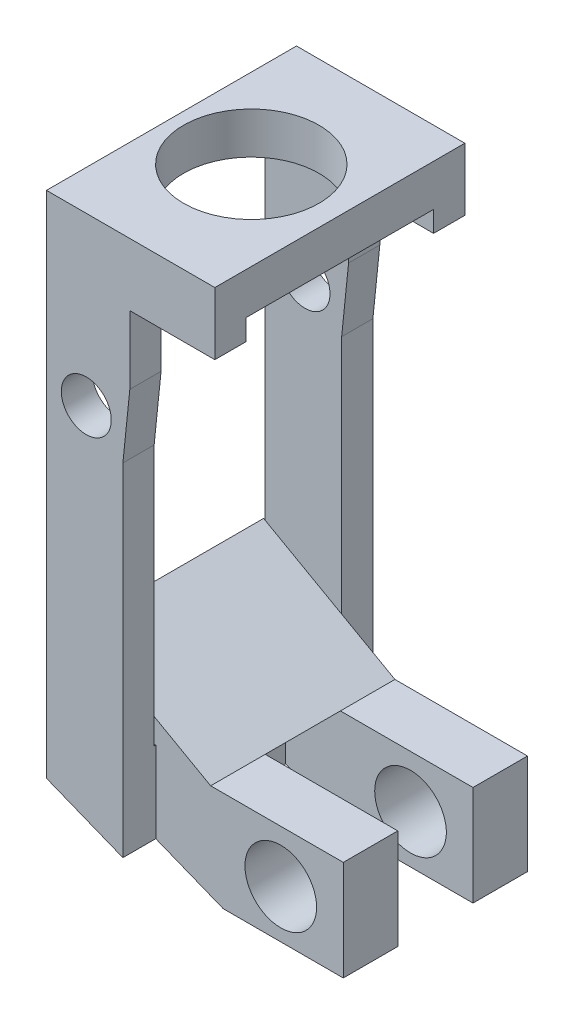
SolidWorks part; units mm, degrees
ref_plane "前视基准面" through (0, 0, 0) normal (0, 0, 1) x (1, 0, 0)
ref_plane "上视基准面" through (0, 0, 0) normal (0, 1, 0) x (1, 0, 0)
ref_plane "右视基准面" through (0, 0, 0) normal (1, 0, 0) x (0, 0, -1)
sketch "草图1" plane through (0, 0, 0) normal (0, 1, 0) x (1, 0, 0)
  line L0 (-4.25, -4.25) -> (-4.25, -6)
  line L2 (4.25, -4.25) -> (4.25, 4.25)
  line L4 (-4.25, -4.25) -> (-4.25, 4.25)
  line L5 (4.25, -4.25) -> (-4.25, 4.25) construction
  line L6 (4.25, 4.25) -> (-4.25, -4.25) construction
  line L7 (4.25, -6) -> (-4.25, -6)
  line L9 (4.25, 6) -> (-4.25, 6)
  line L11 (4.25, -4.25) -> (-4.25, 4.25) construction
  line L12 (4.25, 4.25) -> (-4.25, -4.25) construction
  line L13 (-4.25, 4.25) -> (-4.25, 6)
  line L14 (4.25, 4.25) -> (4.25, 6)
  line L15 (4.25, -4.25) -> (4.25, -6)
  line L16 (4.25, -4.5) -> (-4.25, -4.5)
  line L17 (4.25, 4.5) -> (-4.25, 4.5)
  circle A0 centre (0, 0) radius 3.25
  point P0 (0, 0)
  dimension "D1" = 6.5
  dimension "D2" = 8.5
  dimension "D3" = 8.5
  dimension "D4" = 12
extrude "凸台-拉伸1" add sketch "草图1" along normal blind 2 contours L4 L2 A0 | L7 L9 L4 L2 | L14 L9 L13 region at (-4.1262, 0, 0) region at (0, 0, 5.25) region at (0, 0, -5.25)
extrude "凸台-拉伸2" add sketch "草图1<3>" against normal blind 1 contours L7 L9 L4 L2 | L14 L9 L13 region at (0, 0, 5.25) region at (0, 0, -5.25)
sketch "草图1<3>" plane through (0, 0, 0) normal (0, 1, 0) x (1, 0, 0) same geometry as "草图1"
sketch "草图2" plane through (0, -1, 0) normal (0, -1, 0) x (1, 0, 0)
  line L0 (-3.8309, -6) -> (-3.8309, -4.5)
  line L1 (-3.8309, -6) -> (0.1691, -6)
  line L5 (0.1691, -6) -> (0.1691, -4.5)
  line L6 (-3.8309, 4.5) -> (-3.8309, 6)
  line L7 (-3.8309, 6) -> (0.1691, 6)
  line L11 (0.1691, 4.5) -> (0.1691, 6)
  line L12 (0.1691, 4.5) -> (-3.8309, 4.5)
  line L13 (4.25, 4.5) -> (-4.25, 4.5) construction
  line L14 (0.1691, -4.5) -> (-3.8309, -4.5)
  line L15 (4.25, -4.5) -> (-4.25, -4.5) construction
  dimension "D1" = 4
  dimension "D2" = 4
extrude "凸台-拉伸3" add sketch "草图2" along normal blind 6.5
sketch "草图3" plane through (0, 0, -6) normal (0, 0, -1) x (-1, 0, 0)
  line L0 (-0.1691, -4.2702) -> (0.1633, -7.5)
  line L1 (-0.1691, -7.5) -> (-0.1691, -1) construction
  line L2 (3.8309, -7.5) -> (-0.1691, -7.5) construction
  line L3 (0.1633, -7.5) -> (-0.1691, -7.5)
  line L4 (-0.1691, -7.5) -> (-0.1691, -4.2702)
extrude "切除-拉伸1" cut sketch "草图3" against normal through all
sketch "草图4" plane through (0, 0, -6) normal (0, 0, -1) x (-1, 0, 0)
  line L0 (-4.25, 2) -> (4.25, 2) construction
  circle A0 centre (1.9209, -6) radius 1.2
  dimension "D1" = 2.4
  dimension "D2" = 8
extrude "切除-拉伸2" cut sketch "草图4" against normal through all
sketch "草图5" plane through (0, 0, -6) normal (0, 0, -1) x (-1, 0, 0)
  line L1 (4.25, 2) -> (3.8309, 2)
  line L2 (4.25, 2) -> (4.25, -1)
  line L3 (4.25, -1) -> (3.8309, -1)
  line L4 (3.8309, 2) -> (3.8309, -1)
extrude "切除-拉伸3" cut sketch "草图5" against normal up to surface (12 mm away) up to face at (-3.1209, -6, 6)
sketch "草图7" plane through (0, -7.5, 0) normal (0, -1, 0) x (1, 0, 0)
  line L4 (-3.8309, 4.5) -> (-0.1633, 4.5)
  line L5 (-0.1633, 4.5) -> (-0.1633, 6)
  line L6 (-0.1633, 6) -> (-3.8309, 6)
  line L7 (-3.8309, 6) -> (-3.8309, 4.5)
  line L8 (-3.8309, 4.5) -> (-0.1633, 4.5)
  line L9 (-0.1633, 4.5) -> (-0.1633, 6)
  line L10 (-0.1633, 6) -> (-3.8309, 6)
  line L11 (-3.8309, 6) -> (-3.8309, 4.5)
  line L12 (-0.1633, -6) -> (-0.1633, -4.5)
  line L13 (-0.1633, -4.5) -> (-3.8309, -4.5)
  line L14 (-3.8309, -4.5) -> (-3.8309, -6)
  line L15 (-3.8309, -6) -> (-0.1633, -6)
  line L16 (-0.1633, -6) -> (-0.1633, -4.5)
  line L17 (-0.1633, -4.5) -> (-3.8309, -4.5)
  line L18 (-3.8309, -4.5) -> (-3.8309, -6)
  line L19 (-3.8309, -6) -> (-0.1633, -6)
  dimension "D1" = 0
  dimension "D2" = 0
extrude "凸台-拉伸4" add sketch "草图7" along normal blind 18
sketch "草图8" plane through (0, 0, 4.5) normal (0, 0, -1) x (-1, 0, 0)
  line L0 (0.1633, -25.5) -> (0.1633, -7.5) construction
  line L1 (3.8309, -25.5) -> (0.1633, -25.5)
  line L2 (3.8309, -25.5) -> (3.8309, -20.0174)
  line L3 (3.8309, -20.0174) -> (0.1633, -20.0174)
  line L4 (0.1633, -25.5) -> (0.1633, -20.0174)
extrude "凸台-拉伸5" add sketch "草图8" along normal blind 9
sketch "草图9" plane through (-0.1633, 0, 0) normal (1, 0, 0) x (0, 0, -1)
  line L0 (0, -18.6806) -> (0, -30.4892) construction
  line L1 (1.805, -20.3901) -> (4.4216, -20.3901)
  line L2 (1.805, -20.3901) -> (1.805, -25.1968)
  line L3 (1.805, -25.1968) -> (4.4216, -25.1968)
  line L4 (4.4216, -20.3901) -> (4.4216, -25.1968)
  line L5 (-4.4216, -20.3901) -> (-4.4216, -25.1968)
  line L6 (-1.805, -25.1968) -> (-4.4216, -25.1968)
  line L7 (-1.805, -20.3901) -> (-1.805, -25.1968)
  line L8 (-1.805, -20.3901) -> (-4.4216, -20.3901)
extrude "凸台-拉伸6" add sketch "草图9" along normal blind 9
sketch "草图10" plane through (0, 0, -4.4216) normal (0, 0, -1) x (-1, 0, 0)
  line L0 (-8.8367, -25.1968) -> (-8.8367, -20.3901) construction
  circle A0 centre (-5.8367, -22.8944) radius 1.7192
  dimension "D1" = 3
extrude "切除-拉伸4" cut sketch "草图10" against normal through all
sketch "草图11" plane through (0, 0, -6) normal (0, 0, -1) x (-1, 0, 0)
  line L0 (3.8309, -22.4406) -> (-3.0671, -25.1968)
  line L1 (3.8309, -25.5) -> (3.8309, 2) construction
  line L2 (-8.8367, -25.1968) -> (0.1633, -25.1968) construction
  line L3 (-3.0671, -25.1968) -> (0.3819, -26.6765)
  line L4 (0.3819, -26.6765) -> (3.8309, -26.6765)
  line L5 (3.8309, -26.6765) -> (3.8309, -22.4406)
extrude "切除-拉伸5" cut sketch "草图11" against normal through all
sketch "草图13" plane through (0, 0, -4.4216) normal (0, 0, -1) x (-1, 0, 0)
  line L0 (-2.4715, -20.3901) -> (3.8309, -16.8468)
  line L1 (-8.8367, -20.3901) -> (0.1633, -20.3901) construction
  line L2 (3.8309, -22.4406) -> (3.8309, 2) construction
  line L3 (3.8309, -16.8468) -> (3.8309, -20.3901)
  line L4 (3.8309, -20.3901) -> (-2.4715, -20.3901)
extrude "凸台-拉伸7" add sketch "草图13" against normal up to surface (8.8433 mm away) up to face at (5.8367, -21.1752, 4.4216)
